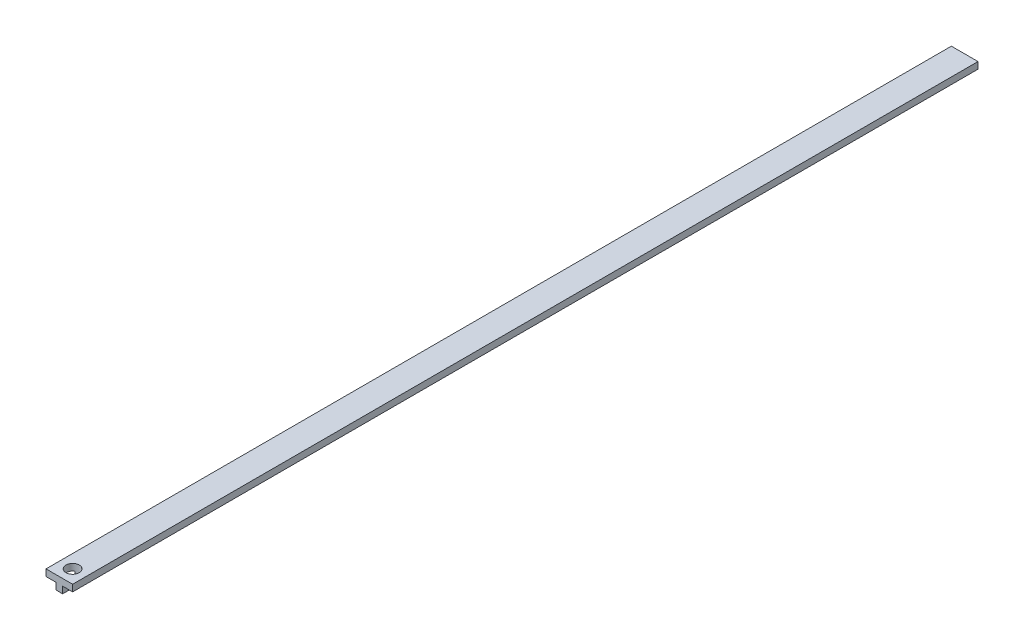
SolidWorks part; units mm, degrees
ref_plane "Front Plane" through (0, 0, 0) normal (0, 0, 1) x (1, 0, 0)
ref_plane "Top Plane" through (0, 0, 0) normal (0, 1, 0) x (1, 0, 0)
ref_plane "Right Plane" through (0, 0, 0) normal (1, 0, 0) x (0, 0, -1)
sketch "Sketch1" plane through (0, 0, 0) normal (0, 0, 1) x (1, 0, 0)
  line L0 (-6.35, 0) -> (6.35, 0) construction
  line L1 (0, -3.175) -> (0, 3.175) construction
  line L5 (-6.35, 3.175) -> (6.35, 3.175) construction
  line L7 (-6.35, 3.175) -> (-6.35, 0) construction
  line L8 (6.35, 0) -> (6.35, 3.175) construction
  line L9 (6.35, 0) -> (-6.35, 0) construction
  line L12 (-1.5875, 0) -> (-1.5875, -3.175) construction
  line L13 (-1.5875, -3.175) -> (1.5875, -3.175) construction
  line L14 (1.5875, -3.175) -> (1.5875, 0) construction
  point P0 (0, 0)
  point P4 (0, 0)
  point P9 (0, 0)
  point P15 (0, 0)
  point P16 (0, -3.175)
  point P22 (0, 3.175)
  point P26 (0, 0)
  dimension "Outside Height" = 6.35
  dimension "Wall Thickness" = 3.175
  dimension "D1" = 3.175
  dimension "Outside Width" = 12.7
sketch "Sketch2" plane through (0, 0, 0) normal (1, 0, 0) x (0, 0, -1)
  line L0 (215.9, 3.175) -> (-215.9, 3.175) construction
  point P3 (-201.295, 3.175)
  point P5 (201.295, 3.175)
  point P7 (0, 3.175)
  dimension "D1" = 14.605
  dimension "D2" = 14.605
  dimension "Length" = 431.8
sketch "Sketch3" plane through (0, 0, 0) normal (0, 0, 1) x (1, 0, 0)
  line L0 (-6.35, 3.175) -> (6.35, 3.175)
  line L10 (6.35, 3.175) -> (6.35, 0)
  line L11 (6.35, 0) -> (1.5875, 0)
  line L12 (1.5875, 0) -> (1.5875, -3.175)
  line L13 (1.5875, -3.175) -> (-1.5875, -3.175)
  line L14 (-1.5875, -3.175) -> (-1.5875, 0)
  line L15 (-1.5875, 0) -> (-6.35, 0)
  line L16 (-6.35, 0) -> (-6.35, 3.175)
extrude "Boss-Extrude1" add sketch "Sketch3" along normal mid plane 431.8
sketch "Sketch4" plane through (0, 3.175, 0) normal (0, 1, 0) x (1, 0, 0)
  line L0 (6.35, -215.9) -> (-6.35, -215.9) construction
  circle A0 centre (0, -209.55) radius 3.175
  point P4 (0, 0)
  dimension "D1" = 6.35
  dimension "D2" = 6.35
extrude "Cut-Extrude1" cut sketch "Sketch4" against normal through all
equation "\"D1@Boss-Extrude1\" = \"Length@Sketch2\""
equation "\"D1@Sketch2\" = \"Outside Width@Sketch1\" * 1.15"
equation "\"D2@Sketch2\"=\"D1@Sketch2\""
equation "\"D1@Sketch1\"=\"Wall Thickness@Sketch1\""
